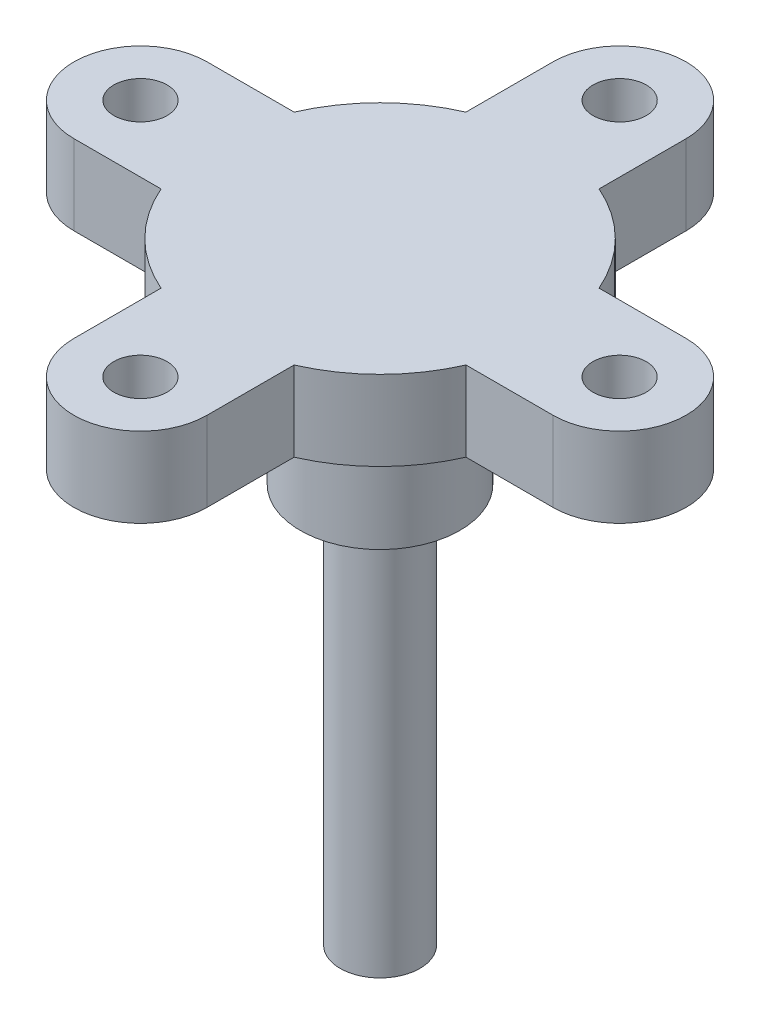
SolidWorks part; units mm, degrees
ref_plane "Front Plane" through (0, 0, 0) normal (0, 0, 1) x (1, 0, 0)
ref_plane "Top Plane" through (0, 0, 0) normal (0, 1, 0) x (1, 0, 0)
ref_plane "Right Plane" through (0, 0, 0) normal (1, 0, 0) x (0, 0, -1)
sketch "Sketch2" plane through (0, -245.0716, 0) normal (0, -1, 0) x (1, 0, 0)
  line L0 (0, 62.5) -> (0, 90.0283) construction
  line L4 (62.5, 0) -> (90, 0) construction
  line L5 (57.2822, 25) -> (90, 25)
  line L6 (57.2822, -25) -> (90, -25)
  line L7 (0, -62.5) -> (0, -90) construction
  line L8 (25, -57.2822) -> (25, -90)
  line L9 (-25, -57.2822) -> (-25, -90)
  line L10 (-25, 57.2822) -> (-25, 90)
  line L13 (25, 57.2822) -> (25, 90)
  line L16 (-57.2822, -25) -> (-90, -25)
  line L17 (-62.5, 0) -> (-90, 0) construction
  line L18 (-57.2822, 25) -> (-90, 25)
  line L20 (0, 62.5) -> (0, 90.0283) construction
  circle A2 centre (0, 90.0283) radius 10
  arc A3 (57.2822, 25) -> (25, 57.2822) centre (0, 0) ccw
  circle A4 centre (90.0283, 0.0283) radius 10
  arc A6 (90, -25) -> (90, 25) centre (90, 0) ccw
  circle A7 centre (0.0283, -90) radius 10
  arc A9 (-25, -90) -> (25, -90) centre (0, -90) ccw
  circle A10 centre (-90, 0) radius 10
  arc A12 (-90, 25) -> (-90, -25) centre (-90, 0) ccw
  arc A14 (25, 90) -> (-25, 90) centre (0, 90.0283) ccw
  arc A15 (-25, 57.2822) -> (-57.2822, 25) centre (0, 0) ccw
  arc A16 (-57.2822, -25) -> (-25, -57.2822) centre (0, 0) ccw
  arc A17 (25, -57.2822) -> (57.2822, -25) centre (0, 0) ccw
  point P2 (0, 45)
  point P4 (0, 45)
  point P17 (-45, 0)
  point P19 (45, 0)
  point P27 (0, -45)
  point P35 (-45, 0)
  point P42 (0.0142, 0.0142)
  dimension "D1" = 20
  dimension "D3" = 125
  dimension "D2" = 50
  dimension "D4" = 4
extrude "Boss-Extrude1" add sketch "Sketch2" along normal blind 30
sketch "Sketch3" plane through (0, -275.0716, 0) normal (0, -1, 0) x (1, 0, 0)
  circle A0 centre (0, 0) radius 30
  circle A1 centre (0, 0) radius 15
  dimension "D1" = 60
  dimension "D2" = 30
extrude "Boss-Extrude2" add sketch "Sketch3" along normal blind 50 contours A0 A1 | A1 | A1 | A0 region at (-29.1515, -275.0716, 0) region at (0, -275.0716, 0)
extrude "Boss-Extrude3" add sketch "Sketch3<3>" along normal blind 200 contours A1 region at (0, -275.0716, 0)
sketch "Sketch3<3>" plane through (0, -275.0716, 0) normal (0, -1, 0) x (1, 0, 0) same geometry as "Sketch3"
fillet "Fillet1" radius 10 1 edges at (0, -325.0716, -15)
scale "Scale1" bodies to scale 106 scale about centroid uniform scaling yes scale factor 0.3
